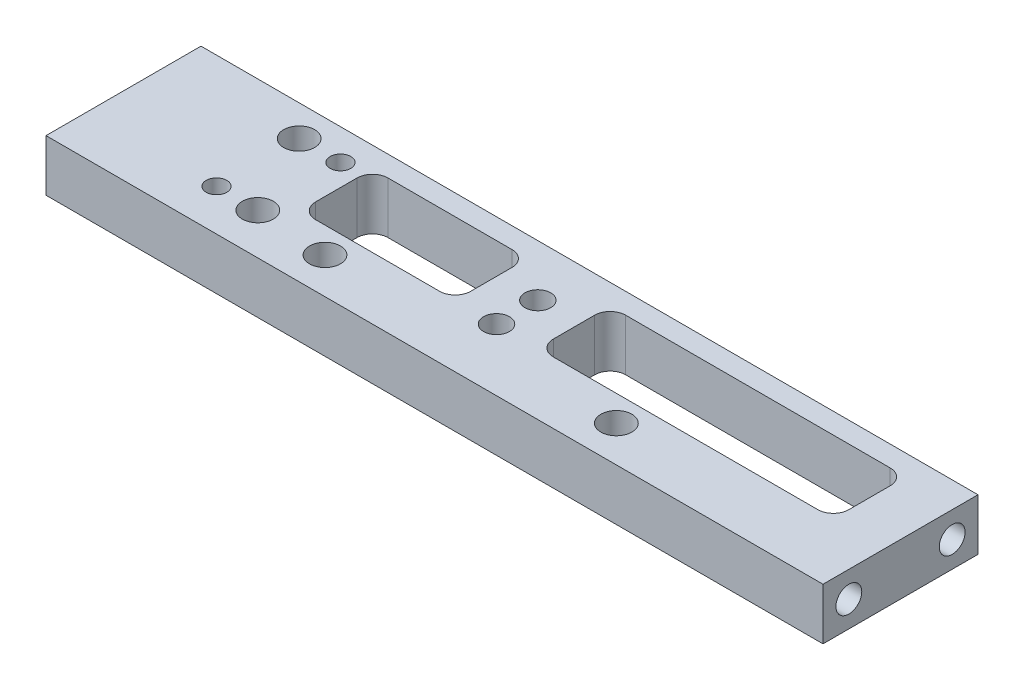
SolidWorks part; units mm, degrees
ref_plane "Front Plane" through (0, 0, 0) normal (0, 0, 1) x (1, 0, 0)
ref_plane "Top Plane" through (0, 0, 0) normal (0, 1, 0) x (1, 0, 0)
ref_plane "Right Plane" through (0, 0, 0) normal (1, 0, 0) x (0, 0, -1)
sketch "Sketch1" plane through (0, 0, 0) normal (1, 0, 0) x (0, 0, -1)
  line L1 (0, 0) -> (15, 0)
  line L2 (15, 0) -> (15, 5)
  line L3 (15, 5) -> (0, 5)
  line L5 (0, 5) -> (0, 0)
  dimension "D1" = 15
  dimension "D2" = 5
extrude "Boss-Extrude1" add sketch "Sketch1" along normal blind 75.2
hole_wizard "Tap Drill for M3x0.5 Tap1" positions "Sketch3" profile "Sketch2" hole size "M3x0.5" standard "ANSI Metric"
sketch "Sketch3" plane through (75.2, 0, 0) normal (1, 0, 0) x (0, 0, -1)
  line L1 (0, 0) -> (15, 0) construction
  line L2 (15, 0) -> (15, 5) construction
  line L4 (12.5, 2.5) -> (2.5, 2.5) construction
  point P2 (2.5, 2.5)
  point P4 (12.5, 2.5)
  dimension "D2" = 2.5
  dimension "D3" = 2.5
  dimension "D4" = 10
sketch "Sketch2" plane through (75.2, 2.5, -2.5) normal (0, 1, 0) x (0, 0, -1)
  line L0 (0, 0) -> (0, 3.7511)
  line L1 (0, 3.7511) -> (1.25, 3)
  line L2 (1.25, 3) -> (1.25, 0)
  line L5 (1.25, 0) -> (0, 0)
  line L10 (0, 3.7511) -> (-1.25, 3) construction
  line L11 (0, -6.35) -> (0, 107.95) construction
  dimension "Hole Dia." = 2.5
  dimension "Hole Depth" = 3
  dimension "Drill Angle" = 118
hole_wizard "Tap Drill for M3x0.5 Tap2" positions "Sketch5" profile "Sketch4" hole size "M3x0.5" standard "ANSI Metric"
sketch "Sketch5" plane through (0, 0, 0) normal (-1, 0, 0) x (0, 0, 1)
  line L0 (-12.5, 2.5) -> (-2.5, 2.5) construction
  line L2 (-15, 5) -> (0, 5) construction
  line L3 (-15, 0) -> (-15, 5) construction
  point P2 (-2.5, 2.5)
  point P4 (-12.5, 2.5)
  dimension "D1" = 2.5
  dimension "D2" = 2.5
  dimension "D3" = 10
sketch "Sketch4" plane through (0, 2.5, -2.5) normal (0, 1, 0) x (0, 0, 1)
  line L0 (0, 0) -> (0, 3.7511)
  line L1 (0, 3.7511) -> (1.25, 3)
  line L2 (1.25, 3) -> (1.25, 0)
  line L5 (1.25, 0) -> (0, 0)
  line L10 (0, 3.7511) -> (-1.25, 3) construction
  line L11 (0, -6.35) -> (0, 107.95) construction
  dimension "Hole Dia." = 2.5
  dimension "Hole Depth" = 3
  dimension "Drill Angle" = 118
sketch "Sketch6" plane through (0, 5, 0) normal (0, 1, 0) x (1, 0, 0)
  line L0 (75.2, 15) -> (0, 15) construction
  line L1 (70.2, 13) -> (41.6, 13)
  line L2 (70.2, 13) -> (70.2, 6)
  line L3 (70.2, 6) -> (41.6, 6)
  line L4 (41.6, 13) -> (41.6, 6)
  line L5 (18.6, 13) -> (33.6, 13)
  line L6 (18.6, 13) -> (18.6, 6)
  line L7 (18.6, 6) -> (33.6, 6)
  line L8 (33.6, 13) -> (33.6, 6)
  line L9 (0, 15) -> (0, 0) construction
  line L10 (75.2, 15) -> (75.2, 0) construction
  line L11 (16.5, 12) -> (12.5, 12) construction
  line L12 (16.5, 12) -> (16.5, 4) construction
  line L13 (16.5, 4) -> (12.5, 4) construction
  line L14 (12.5, 12) -> (12.5, 4) construction
  circle A0 centre (23.5, 3.5) radius 1.5
  circle A1 centre (51.7, 3.5) radius 1.5
  circle A2 centre (12.5, 12) radius 1.5
  circle A3 centre (16.5, 12) radius 1
  circle A4 centre (12.5, 4) radius 1
  circle A5 centre (16.5, 4) radius 1.5
  dimension "D7" = 3
  dimension "D8" = 2
  dimension "D1" = 7
  dimension "D2" = 2
  dimension "D3" = 4
  dimension "D4" = 12.5
  dimension "D5" = 8
  dimension "D6" = 5
  dimension "D9" = 3
  dimension "D10" = 11.5
  dimension "D11" = 8
  dimension "D12" = 23.5
  dimension "D13" = 23.5
  dimension "D14" = 15
  dimension "D15" = 28.6
extrude "Cut-Extrude1" cut sketch "Sketch6" against normal up to next
fillet "Fillet1" radius 1.5 8 edges at (18.6, 2.5, -6) (33.6, 2.5, -6) (33.6, 2.5, -13) (18.6, 2.5, -13) (70.2, 2.5, -6) (41.6, 2.5, -6) (41.6, 2.5, -13) (70.2, 2.5, -13)
chamfer "Chamfer1" distance 1.5 angle 45 2 edges at (16.5, 0, -2.5) (12.5, 0, -10.5)
hole_wizard "Tap Drill for M3x0.5 Tap3" positions "Sketch8" profile "Sketch7" hole size "M3x0.5" standard "ANSI Metric" end condition up to next
sketch "Sketch8" plane through (0, 5, 0) normal (0, 1, 0) x (1, 0, 0)
  line L0 (0, 15) -> (0, 0) construction
  line L1 (75.2, 15) -> (0, 15) construction
  point P0 (37.6, 10)
  point P2 (37.6, 6)
  dimension "D1" = 37.6
  dimension "D2" = 9
  dimension "D3" = 4
sketch "Sketch7" plane through (37.6, 5, -10) normal (1, 0, 0) x (0, 0, 1)
  line L0 (0, 0) -> (0, 5)
  line L1 (0, 5) -> (1.25, 5)
  line L2 (1.25, 5) -> (1.25, 0)
  line L5 (1.25, 0) -> (0, 0)
  line L11 (0, -6.35) -> (0, 107.95) construction
  dimension "Thru Hole Dia." = 2.5
  dimension "Thru Hole Depth" = 5
